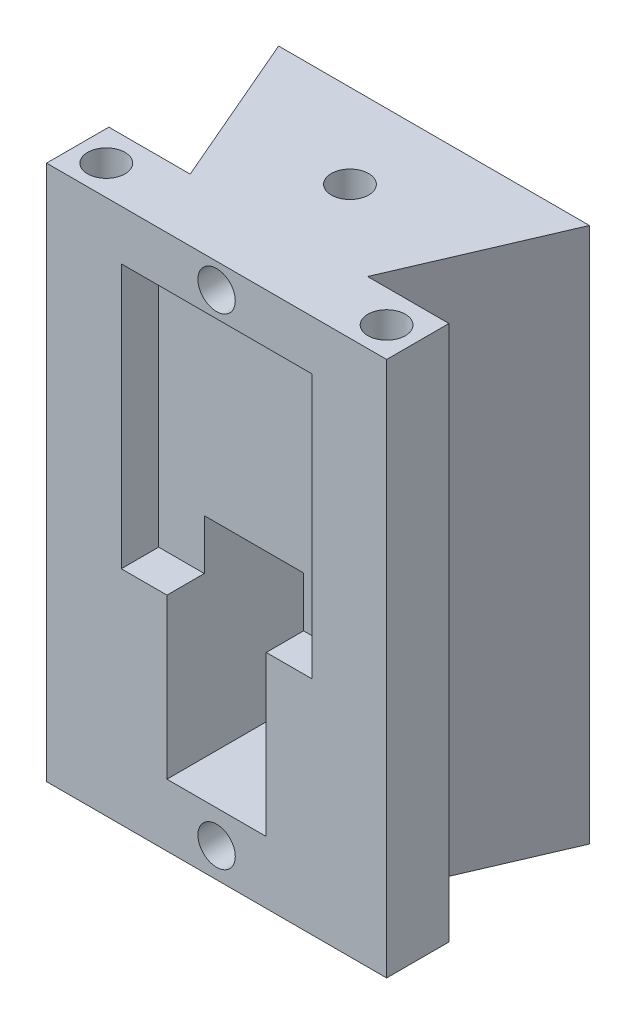
SolidWorks part; units mm, degrees
ref_plane "前视基准面" through (0, 0, 0) normal (0, 0, 1) x (1, 0, 0)
ref_plane "上视基准面" through (0, 0, 0) normal (0, 1, 0) x (1, 0, 0)
ref_plane "右视基准面" through (0, 0, 0) normal (1, 0, 0) x (0, 0, -1)
other "Configuration Table"
sketch "草图2" plane through (0, 0, 0) normal (0, 0, 1) x (1, 0, 0)
  line L1 (-7.65, 10.6) -> (7.65, 10.6)
  line L2 (-7.65, 10.6) -> (-7.65, -10.6)
  line L3 (-7.65, -10.6) -> (7.65, -10.6)
  line L4 (7.65, 10.6) -> (7.65, -10.6)
  line L5 (-7.65, 10.6) -> (7.65, -10.6) construction
  line L6 (-7.65, -10.6) -> (7.65, 10.6) construction
  line L9 (0, 0) -> (0, -50000) construction
  line L10 (-13.65, 14.6) -> (13.65, 14.6)
  line L11 (-13.65, 14.6) -> (-13.65, -14.6)
  line L12 (-13.65, -14.6) -> (13.65, -14.6)
  line L13 (13.65, 14.6) -> (13.65, -14.6)
  line L14 (0, 0) -> (50000, 0) construction
  point P0 (0, 0)
  dimension "D1" = 15.3
  dimension "D2" = 21.2
  dimension "D3" = 4
  dimension "D4" = 4
  dimension "D5" = 6
extrude "凸台-拉伸1" add sketch "草图2" along normal blind 5
extrude "凸台-拉伸2" add sketch "草图2<3>" along normal blind 2 contours L4 L1 L2 L3 region at (0, 0, 0)
sketch "草图2<3>" plane through (0, 0, 0) normal (0, 0, 1) x (1, 0, 0) same geometry as "草图2"
sketch "草图5" plane through (0, -10.6, 0) normal (0, 1, 0) x (1, 0, 0)
  line L0 (0, 0) -> (0, -14.0073) construction
  line L1 (-3.9855, -1.995) -> (3.9855, -1.995)
  line L2 (-3.9855, -1.995) -> (-3.9855, -5.3522)
  line L3 (-3.9855, -5.3522) -> (3.9855, -5.3522)
  line L4 (3.9855, -1.995) -> (3.9855, -5.3522)
extrude "切除-拉伸2" cut sketch "草图5" against normal blind 7
sketch "草图6" plane through (0, -14.6, 0) normal (0, -1, 0) x (1, 0, 0)
  line L0 (0, 0) -> (0, -12.7802) construction
  circle A0 centre (-11.25, 2.6037) radius 1.5
  circle A1 centre (11.25, 2.6037) radius 1.5
  dimension "D1" = 3
  dimension "D2" = 22.5
extrude "切除-拉伸3" cut sketch "草图6" against normal through all both and the other way through all
sketch "草图7" plane through (0, -14.6, 0) normal (0, -1, 0) x (1, 0, 0)
  line L0 (0, 0) -> (0, -14.4913) construction
  line L2 (-13.65, 0) -> (13.65, 0) construction
  line L4 (7.1187, 0) -> (-7.1187, 0)
  line L5 (-7.1187, 0) -> (-12.4765, -12.4538)
  line L6 (-12.4765, -12.4538) -> (12.4765, -12.4538)
  line L7 (12.4765, -12.4538) -> (7.1187, 0)
  circle A0 centre (0, -5.7069) radius 1.5
  point P11 (-12.4765, -12.4538)
  dimension "D1" = 3
extrude "凸台-拉伸3" add sketch "草图7" against normal up to surface (29.2 mm away) up to face at (-9.75, 14.6, 2.6037)
sketch "草图8" plane through (0, 0, 5) normal (0, 0, 1) x (1, 0, 0)
  line L0 (0, 10.6) -> (0, -49989.4) construction
  line L1 (7.65, 10.6) -> (-7.65, 10.6) construction
  line L2 (-7.65, 10.6) -> (7.65, 10.6) construction
  circle A0 centre (0, 12.6) radius 1.5
  point P4 (0, 10.6)
  dimension "D1" = 3
  dimension "D2" = 2
extrude "切除-拉伸4" cut sketch "草图8" against normal blind 6
sketch "草图9" plane through (0, 0, 2) normal (0, 0, 1) x (1, 0, 0)
  line L0 (0, 0) -> (0, -21.8388) construction
  line L1 (-3.9855, -15.2007) -> (3.9855, -15.2007)
  line L2 (-3.9855, -15.2007) -> (-3.9855, -6.5767)
  line L3 (-3.9855, -6.5767) -> (3.9855, -6.5767)
  line L4 (3.9855, -15.2007) -> (3.9855, -6.5767)
  line L5 (-3.9855, -10.6) -> (-3.9855, -14.6) construction
extrude "切除-拉伸5" cut sketch "草图9" against normal through all
sketch "草图10" plane through (0, -14.6, 0) normal (0, -1, 0) x (1, 0, 0)
  line L0 (-13.65, 5) -> (-13.65, 0)
  line L1 (-13.65, 0) -> (-7.1187, 0)
  line L4 (-3.9855, 5) -> (-13.65, 5)
  line L7 (7.1187, 0) -> (13.65, 0)
  line L8 (13.65, 0) -> (13.65, 5)
  line L9 (13.65, 5) -> (3.9855, 5)
  line L10 (-7.1187, 0) -> (-12.4765, -12.4538)
  line L11 (-12.4765, -12.4538) -> (-3.9855, -12.4538)
  line L12 (-3.9855, -12.4538) -> (-3.9855, 5)
  line L13 (3.9855, 5) -> (3.9855, -12.4538)
  line L14 (3.9855, -12.4538) -> (12.4765, -12.4538)
  line L15 (12.4765, -12.4538) -> (7.1187, 0)
  circle A0 centre (-11.25, 2.6037) radius 1.5
  circle A1 centre (11.25, 2.6037) radius 1.5
extrude "凸台-拉伸4" add sketch "草图10" along normal blind 13.8
sketch "草图12" plane through (0, 0, -12.4538) normal (0, 0, -1) x (-1, 0, 0)
  line L0 (-3.9855, -6.5767) -> (-3.9855, -28.4) construction
  line L1 (-3.9855, -23.3971) -> (3.9855, -23.3971)
  line L2 (-3.9855, -23.3971) -> (-3.9855, -28.4)
  line L3 (-3.9855, -28.4) -> (3.9855, -28.4)
  line L4 (3.9855, -23.3971) -> (3.9855, -28.4)
extrude "凸台-拉伸5" add sketch "草图12" against normal up to surface (17.4538 mm away)
sketch "草图13" plane through (0, 0, 5) normal (0, 0, 1) x (1, 0, 0)
  circle A0 centre (0, -26.0287) radius 1.5
extrude "切除-拉伸6" cut sketch "草图13" against normal through all
